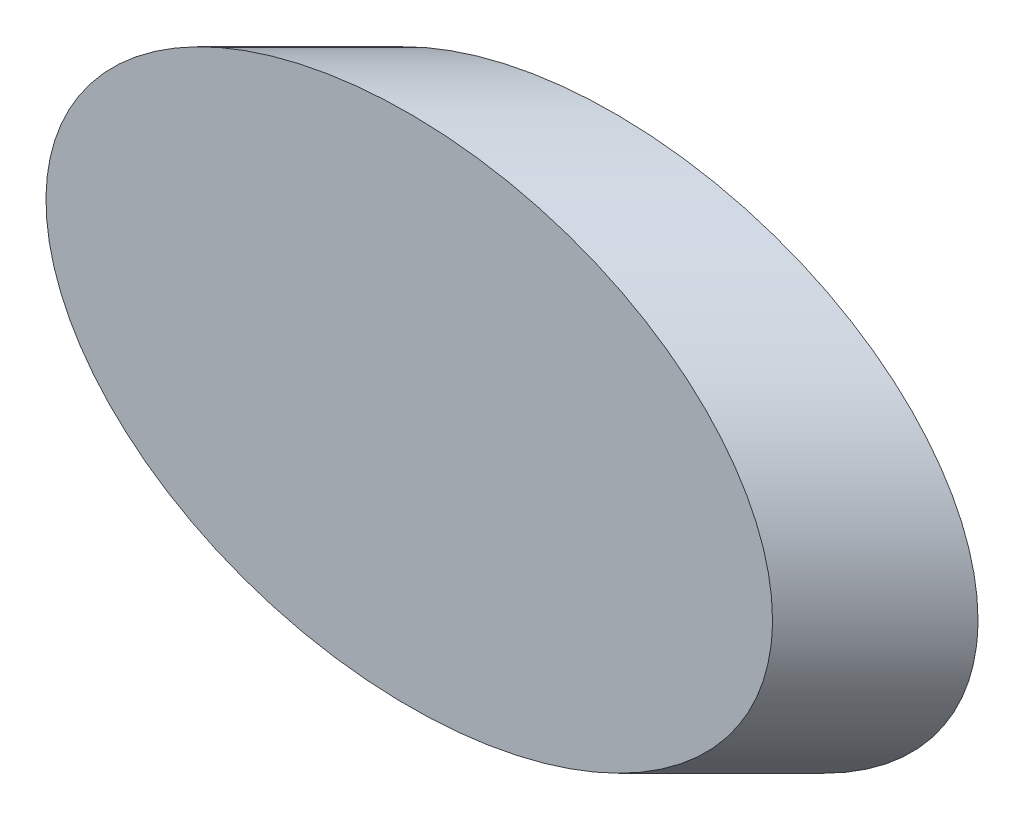
SolidWorks part; units mm, degrees
material "Glass"
ref_plane "Front Plane" through (0, 0, 0) normal (0, 0, 1) x (1, 0, 0)
ref_plane "Top Plane" through (0, 0, 0) normal (0, 1, 0) x (1, 0, 0)
ref_plane "Right Plane" through (0, 0, 0) normal (1, 0, 0) x (0, 0, -1)
sketch "Sketch2" plane through (0, 0, 0) normal (0, 0, 1) x (1, 0, 0)
  circle A0 centre (0, 0) radius 50
  dimension "D1" = 100
extrude "Boss-Extrude1" add sketch "Sketch2" against normal blind 10 contours A0
ref_axis "Axis1" through (0, 27.5, 0) along (0, -1, 0)
ref_plane "Plane1" through (0, 0, 0) normal (-0.7071, 0, 0.7071) x (0.7071, 0, 0.7071)
sketch "Sketch3" plane through (0, 0, 0) normal (-0.7071, 0, 0.7071) x (0.7071, 0, 0.7071)
  circle A0 centre (0, 0) radius 75
  circle A1 centre (0, 0) radius 25
  dimension "D1" = 50
  dimension "D2" = 150
extrude "Cut-Extrude1" cut sketch "Sketch3" along normal through all both and the other way through all
